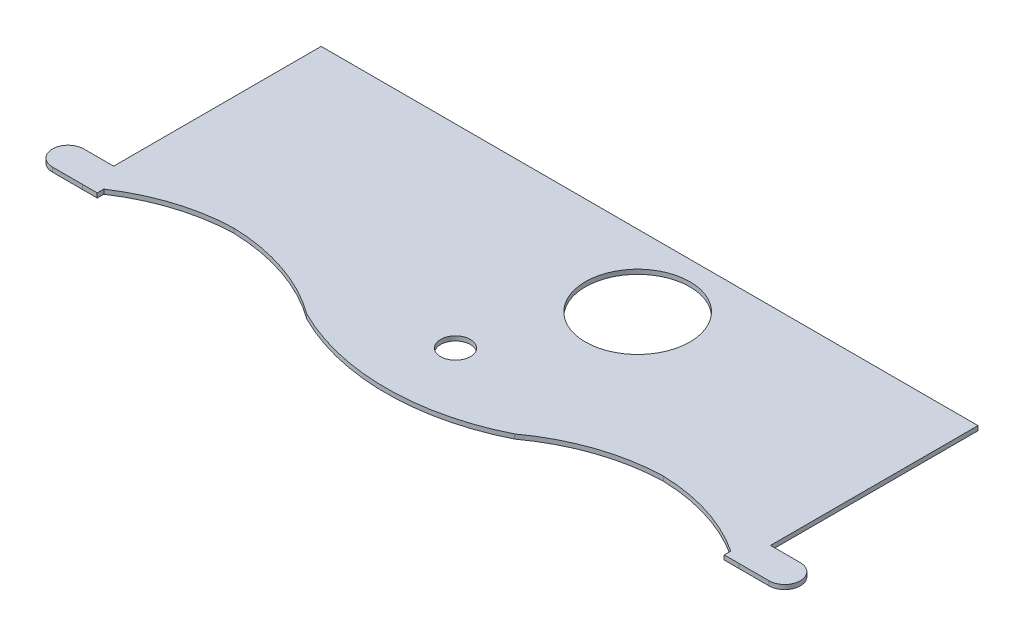
SolidWorks part; units mm, degrees
ref_plane "Front Plane" through (0, 0, 0) normal (0, 0, 1) x (1, 0, 0)
ref_plane "Top Plane" through (0, 0, 0) normal (0, 1, 0) x (1, 0, 0)
ref_plane "Right Plane" through (0, 0, 0) normal (1, 0, 0) x (0, 0, -1)
ref_plane "Plane1" through (0, 4.5, 0) normal (0, 1, 0) x (1, 0, 0)
ref_plane "Plane2" through (0, 3, 0) normal (0, -1, 0) x (-1, 0, 0)
sketch "Sketch1" plane through (0, 3, 0) normal (0, -1, 0) x (-1, 0, 0)
  line L0 (0, -100) -> (0, 70) construction
  line L3 (110, 50) -> (-110, 50)
  line L5 (-34.8399, -30) -> (34.8399, -30) construction
  line L6 (-110, 50) -> (-110, -19.5)
  line L7 (-110, -30) -> (-105, -30.0025)
  line L8 (-105, -30.0025) -> (-105, -27.799)
  line L9 (110, 50) -> (110, -19.5)
  line L10 (110, -30) -> (105, -30.0025)
  line L11 (105, -30.0025) -> (105, -27.799)
  line L12 (-110, -19.5) -> (-120, -19.5)
  line L14 (-120, -30) -> (-110, -30)
  line L15 (110, -19.5) -> (120, -19.5)
  line L17 (120, -30) -> (110, -30)
  line L18 (-120, -19.5) -> (-120, -30) construction
  line L19 (120, -19.5) -> (120, -30) construction
  arc A0 (-105, -27.799) -> (-71.9147, -17.3273) centre (-70.2175, -80.192) cw
  arc A1 (-71.9147, -17.3273) -> (-105, -27.799) centre (-70.2175, -80.192) ccw construction
  arc A2 (-71.9147, -17.3273) -> (-34.8399, -30) centre (-73.6989, -83.1159) cw
  arc A3 (-34.8399, -30) -> (-71.9147, -17.3273) centre (-73.6989, -83.1159) ccw construction
  arc A4 (-34.8399, -30) -> (34.8399, -30) centre (0, 39.341) ccw
  arc A5 (-120, -19.5) -> (-120, -30) centre (-120, -24.75) ccw
  arc A6 (34.8399, -30) -> (71.9147, -17.3273) centre (73.6989, -83.1159) cw
  arc A7 (71.9147, -17.3273) -> (34.8399, -30) centre (73.6989, -83.1159) ccw construction
  arc A8 (71.9147, -17.3273) -> (105, -27.799) centre (70.2175, -80.192) cw
  arc A9 (105, -27.799) -> (71.9147, -17.3273) centre (70.2175, -80.192) ccw construction
  circle A11 centre (0, -15) radius 5
  circle A12 centre (-20, 26) radius 17.5
  circle A13 centre (-20, 26) radius 17.5 construction
  circle A14 centre (0, -15) radius 5 construction
  arc A15 (-34.8399, -30) -> (34.8399, -30) centre (0, 39.341) ccw construction
  arc A16 (120, -30) -> (120, -19.5) centre (120, -24.75) ccw
extrude "Boss-Extrude1" add sketch "Sketch1" against normal up to surface (1.5 mm away) up to plane "Plane1"
